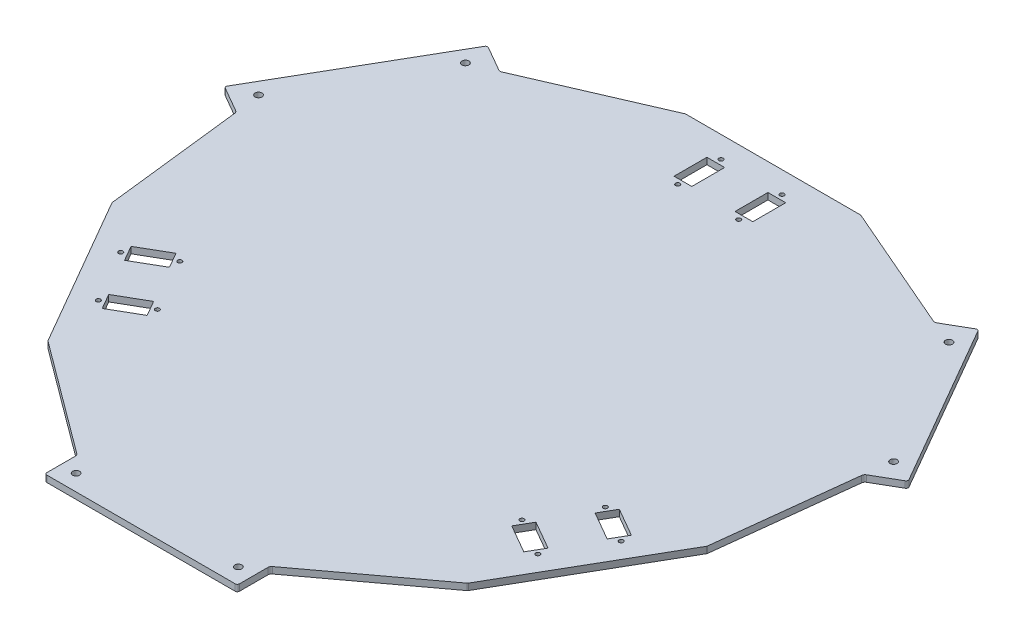
SolidWorks part; units mm, degrees
ref_plane "正面" through (0, 0, 0) normal (0, 0, 1) x (1, 0, 0)
ref_plane "平面" through (0, 0, 0) normal (0, 1, 0) x (1, 0, 0)
ref_plane "右側面" through (0, 0, 0) normal (1, 0, 0) x (0, 0, -1)
sketch "ｽｹｯﾁ1" plane through (0, 0, 0) normal (0, 1, 0) x (1, 0, 0)
  line L4 (82.0098, -128.7548) -> (95.0002, -136.2548)
  line L5 (152.5098, -6.6452) -> (82.0098, -128.7548)
  line L6 (178.6972, -21.2874) -> (185.4854, -9.5298)
  line L7 (185.4854, -7.7798) -> (158.8752, 38.3104)
  line L8 (156.4847, 38.9509) -> (145.7723, 32.7661)
  line L9 (144.9088, 31.4513) -> (137.6417, -31.4843)
  line L10 (138.5051, -33.2006) -> (149.5636, -39.5852)
  line L11 (151.4028, -39.53) -> (178.1458, -21.8728)
  line L12 (178.6972, -21.2874) -> (185.4854, -9.5298)
  line L13 (185.4854, -7.7798) -> (158.8752, 38.3104)
  line L14 (156.4847, 38.9509) -> (145.7723, 32.7661)
  line L15 (144.9088, 31.4513) -> (137.6417, -31.4843)
  line L16 (138.5051, -33.2006) -> (149.5636, -39.5852)
  line L17 (151.4028, -39.53) -> (178.1458, -21.8728)
  line L18 (101.2625, 109.8594) -> (111.9748, 116.0442)
  line L19 (112.6154, 118.4348) -> (86.0052, 164.525)
  line L20 (84.4896, 165.4) -> (70.9131, 165.4)
  line L21 (70.1305, 165.2152) -> (41.4674, 150.8837)
  line L22 (40.5, 149.3184) -> (40.5, 136.5492)
  line L23 (41.5546, 134.9433) -> (99.6921, 109.7691)
  line L24 (101.2625, 109.8594) -> (111.9748, 116.0442)
  line L25 (112.6154, 118.4348) -> (86.0052, 164.525)
  line L26 (84.4896, 165.4) -> (70.9131, 165.4)
  line L27 (70.1305, 165.2152) -> (41.4674, 150.8837)
  line L28 (40.5, 149.3184) -> (40.5, 136.5492)
  line L29 (41.5546, 134.9433) -> (99.6921, 109.7691)
  line L30 (165.5002, -14.1452) -> (152.5098, -6.6452)
  line L31 (95.0002, -136.2548) -> (165.5002, -14.1452)
  line L32 (82.0098, -128.7548) -> (95.0002, -136.2548)
  line L33 (152.5098, -6.6452) -> (82.0098, -128.7548)
  line L34 (165.5002, -14.1452) -> (152.5098, -6.6452)
  line L35 (95.0002, -136.2548) -> (165.5002, -14.1452)
  line L36 (70.5, 135.4) -> (70.5, 150.4)
  line L37 (-70.5, 135.4) -> (70.5, 135.4)
  line L38 (-70.5, 150.4) -> (-70.5, 135.4)
  line L39 (70.5, 150.4) -> (-70.5, 150.4)
  line L40 (70.5, 135.4) -> (70.5, 150.4)
  line L41 (-70.5, 135.4) -> (70.5, 135.4)
  line L42 (-70.5, 150.4) -> (-70.5, 135.4)
  line L43 (70.5, 150.4) -> (-70.5, 150.4)
  line L44 (-74.5098, -141.7452) -> (-74.5098, -156.7452)
  line L45 (74.5102, -141.7452) -> (-74.5098, -141.7452)
  line L46 (-86.0052, 164.525) -> (-112.6154, 118.4348)
  line L47 (-70.9131, 165.4) -> (-84.4896, 165.4)
  line L48 (-41.4674, 150.8837) -> (-70.1305, 165.2152)
  line L49 (-40.5, 136.5492) -> (-40.5, 149.3184)
  line L50 (-99.6921, 109.7691) -> (-41.5546, 134.9433)
  line L51 (-111.9748, 116.0442) -> (-101.2625, 109.8594)
  line L52 (-86.0052, 164.525) -> (-112.6154, 118.4348)
  line L53 (-70.9131, 165.4) -> (-84.4896, 165.4)
  line L54 (-41.4674, 150.8837) -> (-70.1305, 165.2152)
  line L55 (-40.5, 136.5492) -> (-40.5, 149.3184)
  line L56 (-99.6921, 109.7691) -> (-41.5546, 134.9433)
  line L57 (-111.9748, 116.0442) -> (-101.2625, 109.8594)
  line L58 (108.0154, -143.3424) -> (109.9354, -111.3536)
  line L59 (100.9958, -155.8702) -> (107.784, -144.1126)
  line L60 (46.2598, -156.7452) -> (99.4802, -156.7452)
  line L61 (44.5098, -142.6256) -> (44.5098, -154.9952)
  line L62 (96.087, -103.459) -> (45.2168, -141.2204)
  line L63 (109.0636, -109.7332) -> (98.0051, -103.3487)
  line L64 (108.0154, -143.3424) -> (109.9354, -111.3536)
  line L65 (100.9958, -155.8702) -> (107.784, -144.1126)
  line L66 (46.2598, -156.7452) -> (99.4802, -156.7452)
  line L67 (44.5098, -142.6256) -> (44.5098, -154.9952)
  line L68 (96.087, -103.459) -> (45.2168, -141.2204)
  line L69 (109.0636, -109.7332) -> (98.0051, -103.3487)
  line L70 (74.5102, -156.7452) -> (74.5102, -141.7452)
  line L71 (-74.5098, -156.7452) -> (74.5102, -156.7452)
  line L72 (-74.5098, -141.7452) -> (-74.5098, -156.7452)
  line L73 (74.5102, -141.7452) -> (-74.5098, -141.7452)
  line L74 (74.5102, -156.7452) -> (74.5102, -141.7452)
  line L75 (-74.5098, -156.7452) -> (74.5102, -156.7452)
  line L76 (-152.5098, -6.6452) -> (-165.5002, -14.1452)
  line L77 (-82.0098, -128.7548) -> (-152.5098, -6.6452)
  line L78 (-95.0002, -136.2548) -> (-82.0098, -128.7548)
  line L79 (-165.5002, -14.1452) -> (-95.0002, -136.2548)
  line L80 (-152.5098, -6.6452) -> (-165.5002, -14.1452)
  line L81 (-82.0098, -128.7548) -> (-152.5098, -6.6452)
  line L82 (-95.0002, -136.2548) -> (-82.0098, -128.7548)
  line L83 (-165.5002, -14.1452) -> (-95.0002, -136.2548)
  line L84 (173.0004, 13.8449) -> (98.4904, 142.9)
  line L85 (160.01, 6.3449) -> (173.0004, 13.8449)
  line L86 (-99.4802, -156.7452) -> (-46.2598, -156.7452)
  line L87 (-107.784, -144.1126) -> (-100.9958, -155.8702)
  line L88 (-109.9354, -111.3536) -> (-108.0154, -143.3424)
  line L89 (-98.0051, -103.3487) -> (-109.0636, -109.7332)
  line L90 (-45.2168, -141.2204) -> (-96.087, -103.459)
  line L91 (-44.5098, -154.9952) -> (-44.5098, -142.6256)
  line L92 (-99.4802, -156.7452) -> (-46.2598, -156.7452)
  line L93 (-107.784, -144.1126) -> (-100.9958, -155.8702)
  line L94 (-109.9354, -111.3536) -> (-108.0154, -143.3424)
  line L95 (-98.0051, -103.3487) -> (-109.0636, -109.7332)
  line L96 (-45.2168, -141.2204) -> (-96.087, -103.459)
  line L97 (-44.5098, -154.9952) -> (-44.5098, -142.6256)
  line L98 (-185.4854, -9.5298) -> (-178.6972, -21.2874)
  line L99 (-158.8752, 38.3104) -> (-185.4854, -7.7798)
  line L100 (-145.7723, 32.7661) -> (-156.4847, 38.9509)
  line L101 (-137.6417, -31.4843) -> (-144.9088, 31.4513)
  line L102 (-149.5636, -39.5852) -> (-138.5051, -33.2006)
  line L103 (-178.1458, -21.8728) -> (-151.4028, -39.53)
  line L104 (-185.4854, -9.5298) -> (-178.6972, -21.2874)
  line L105 (-158.8752, 38.3104) -> (-185.4854, -7.7798)
  line L106 (-145.7723, 32.7661) -> (-156.4847, 38.9509)
  line L107 (-137.6417, -31.4843) -> (-144.9088, 31.4513)
  line L108 (-149.5636, -39.5852) -> (-138.5051, -33.2006)
  line L109 (-178.1458, -21.8728) -> (-151.4028, -39.53)
  line L110 (85.5, 135.4) -> (160.01, 6.3449)
  line L111 (98.4904, 142.9) -> (85.5, 135.4)
  line L112 (173.0004, 13.8449) -> (98.4904, 142.9)
  line L113 (160.01, 6.3449) -> (173.0004, 13.8449)
  line L114 (85.5, 135.4) -> (160.01, 6.3449)
  line L115 (98.4904, 142.9) -> (85.5, 135.4)
  line L116 (-173.0004, 13.8449) -> (-160.01, 6.3449)
  line L117 (-160.01, 6.3449) -> (-85.5, 135.4)
  line L118 (-85.5, 135.4) -> (-98.4904, 142.9)
  line L119 (-98.4904, 142.9) -> (-173.0004, 13.8449)
  line L120 (-173.0004, 13.8449) -> (-160.01, 6.3449)
  line L121 (-160.01, 6.3449) -> (-85.5, 135.4)
  line L122 (-85.5, 135.4) -> (-98.4904, 142.9)
  line L123 (-98.4904, 142.9) -> (-173.0004, 13.8449)
  line L858 (-40.5, 149.3184) -> (-40.5, 150.4)
  line L859 (40.5, 149.3184) -> (40.5, 150.4)
  line L860 (111.9748, 116.0442) -> (113.4904, 116.9192)
  line L861 (156.4847, 38.9509) -> (158.0002, 39.8259)
  line L862 (149.5636, -39.5852) -> (150.5002, -40.126)
  line L863 (109.0636, -109.7332) -> (110.0002, -110.274)
  line L864 (-109.0636, -109.7332) -> (-110.0002, -110.274)
  line L865 (-149.5636, -39.5852) -> (-150.5002, -40.126)
  line L866 (-156.4847, 38.9509) -> (-158.0002, 39.8259)
  line L867 (-111.9748, 116.0442) -> (-113.4904, 116.9192)
  line L868 (96.087, -103.459) -> (97.0098, -102.774)
  line L869 (-44.5098, -154.9952) -> (-44.5098, -156.7452)
  line L3810 (-41.5546, 134.9433) -> (-40.5, 135.4)
  line L3811 (41.5546, 134.9433) -> (40.5, 135.4)
  line L3812 (44.5098, -154.9952) -> (44.5098, -156.7452)
  line L3813 (-137.6417, -31.4843) -> (-137.5098, -32.626)
  line L3814 (-96.087, -103.459) -> (-97.0098, -102.774)
  line L3815 (137.6417, -31.4843) -> (137.5098, -32.626)
  arc A6 (185.4854, -9.5298) -> (185.4854, -7.7798) centre (183.9699, -8.6548) ccw
  arc A7 (158.8752, 38.3104) -> (156.4847, 38.9509) centre (157.3597, 37.4354) ccw
  arc A8 (145.7723, 32.7661) -> (144.9088, 31.4513) centre (146.6473, 31.2506) ccw
  arc A9 (137.6417, -31.4843) -> (138.5051, -33.2006) centre (139.3801, -31.685) ccw
  arc A10 (149.5636, -39.5852) -> (151.4028, -39.53) centre (150.4386, -38.0696) ccw
  arc A11 (178.1458, -21.8728) -> (178.6972, -21.2874) centre (177.1816, -20.4124) ccw
  arc A12 (185.4854, -9.5298) -> (185.4854, -7.7798) centre (183.9699, -8.6548) ccw
  arc A13 (158.8752, 38.3104) -> (156.4847, 38.9509) centre (157.3597, 37.4354) ccw
  arc A14 (145.7723, 32.7661) -> (144.9088, 31.4513) centre (146.6473, 31.2506) ccw
  arc A15 (137.6417, -31.4843) -> (138.5051, -33.2006) centre (139.3801, -31.685) ccw
  arc A16 (149.5636, -39.5852) -> (151.4028, -39.53) centre (150.4386, -38.0696) ccw
  arc A17 (178.1458, -21.8728) -> (178.6972, -21.2874) centre (177.1816, -20.4124) ccw
  arc A18 (111.9748, 116.0442) -> (112.6154, 118.4348) centre (111.0998, 117.5598) ccw
  arc A19 (86.0052, 164.525) -> (84.4896, 165.4) centre (84.4896, 163.65) ccw
  arc A20 (70.9131, 165.4) -> (70.1305, 165.2152) centre (70.9131, 163.65) ccw
  arc A21 (41.4674, 150.8837) -> (40.5, 149.3184) centre (42.25, 149.3184) ccw
  arc A22 (40.5, 136.5492) -> (41.5546, 134.9433) centre (42.25, 136.5492) ccw
  arc A23 (99.6921, 109.7691) -> (101.2625, 109.8594) centre (100.3875, 111.375) ccw
  arc A24 (111.9748, 116.0442) -> (112.6154, 118.4348) centre (111.0998, 117.5598) ccw
  arc A25 (86.0052, 164.525) -> (84.4896, 165.4) centre (84.4896, 163.65) ccw
  arc A26 (70.9131, 165.4) -> (70.1305, 165.2152) centre (70.9131, 163.65) ccw
  arc A27 (41.4674, 150.8837) -> (40.5, 149.3184) centre (42.25, 149.3184) ccw
  arc A28 (40.5, 136.5492) -> (41.5546, 134.9433) centre (42.25, 136.5492) ccw
  arc A29 (99.6921, 109.7691) -> (101.2625, 109.8594) centre (100.3875, 111.375) ccw
  arc A30 (-84.4896, 165.4) -> (-86.0052, 164.525) centre (-84.4896, 163.65) ccw
  arc A31 (-70.1305, 165.2152) -> (-70.9131, 165.4) centre (-70.9131, 163.65) ccw
  arc A32 (-40.5, 149.3184) -> (-41.4674, 150.8837) centre (-42.25, 149.3184) ccw
  arc A33 (-41.5546, 134.9433) -> (-40.5, 136.5492) centre (-42.25, 136.5492) ccw
  arc A34 (-101.2625, 109.8594) -> (-99.6921, 109.7691) centre (-100.3875, 111.375) ccw
  arc A35 (-112.6154, 118.4348) -> (-111.9748, 116.0442) centre (-111.0998, 117.5598) ccw
  arc A36 (-84.4896, 165.4) -> (-86.0052, 164.525) centre (-84.4896, 163.65) ccw
  arc A37 (-70.1305, 165.2152) -> (-70.9131, 165.4) centre (-70.9131, 163.65) ccw
  arc A38 (-40.5, 149.3184) -> (-41.4674, 150.8837) centre (-42.25, 149.3184) ccw
  arc A39 (-41.5546, 134.9433) -> (-40.5, 136.5492) centre (-42.25, 136.5492) ccw
  arc A40 (-101.2625, 109.8594) -> (-99.6921, 109.7691) centre (-100.3875, 111.375) ccw
  arc A41 (-112.6154, 118.4348) -> (-111.9748, 116.0442) centre (-111.0998, 117.5598) ccw
  arc A42 (107.784, -144.1126) -> (108.0154, -143.3424) centre (106.2685, -143.2376) ccw
  arc A43 (99.4802, -156.7452) -> (100.9958, -155.8702) centre (99.4802, -154.9952) ccw
  arc A44 (44.5098, -154.9952) -> (46.2598, -156.7452) centre (46.2598, -154.9952) ccw
  arc A45 (45.2168, -141.2204) -> (44.5098, -142.6256) centre (46.2598, -142.6256) ccw
  arc A46 (98.0051, -103.3487) -> (96.087, -103.459) centre (97.1301, -104.8642) ccw
  arc A47 (109.9354, -111.3536) -> (109.0636, -109.7332) centre (108.1886, -111.2488) ccw
  arc A48 (107.784, -144.1126) -> (108.0154, -143.3424) centre (106.2685, -143.2376) ccw
  arc A49 (99.4802, -156.7452) -> (100.9958, -155.8702) centre (99.4802, -154.9952) ccw
  arc A50 (44.5098, -154.9952) -> (46.2598, -156.7452) centre (46.2598, -154.9952) ccw
  arc A51 (45.2168, -141.2204) -> (44.5098, -142.6256) centre (46.2598, -142.6256) ccw
  arc A52 (98.0051, -103.3487) -> (96.087, -103.459) centre (97.1301, -104.8642) ccw
  arc A53 (109.9354, -111.3536) -> (109.0636, -109.7332) centre (108.1886, -111.2488) ccw
  arc A54 (-100.9958, -155.8702) -> (-99.4802, -156.7452) centre (-99.4802, -154.9952) ccw
  arc A55 (-108.0154, -143.3424) -> (-107.784, -144.1126) centre (-106.2685, -143.2376) ccw
  arc A56 (-109.0636, -109.7332) -> (-109.9354, -111.3536) centre (-108.1886, -111.2488) ccw
  arc A57 (-96.087, -103.459) -> (-98.0051, -103.3487) centre (-97.1301, -104.8642) ccw
  arc A58 (-44.5098, -142.6256) -> (-45.2168, -141.2204) centre (-46.2598, -142.6256) ccw
  arc A59 (-46.2598, -156.7452) -> (-44.5098, -154.9952) centre (-46.2598, -154.9952) ccw
  arc A60 (-100.9958, -155.8702) -> (-99.4802, -156.7452) centre (-99.4802, -154.9952) ccw
  arc A61 (-108.0154, -143.3424) -> (-107.784, -144.1126) centre (-106.2685, -143.2376) ccw
  arc A62 (-109.0636, -109.7332) -> (-109.9354, -111.3536) centre (-108.1886, -111.2488) ccw
  arc A63 (-96.087, -103.459) -> (-98.0051, -103.3487) centre (-97.1301, -104.8642) ccw
  arc A64 (-44.5098, -142.6256) -> (-45.2168, -141.2204) centre (-46.2598, -142.6256) ccw
  arc A65 (-46.2598, -156.7452) -> (-44.5098, -154.9952) centre (-46.2598, -154.9952) ccw
  arc A66 (-185.4854, -7.7798) -> (-185.4854, -9.5298) centre (-183.9699, -8.6548) ccw
  arc A67 (-156.4847, 38.9509) -> (-158.8752, 38.3104) centre (-157.3597, 37.4354) ccw
  arc A68 (-144.9088, 31.4513) -> (-145.7723, 32.7661) centre (-146.6473, 31.2506) ccw
  arc A69 (-138.5051, -33.2006) -> (-137.6417, -31.4843) centre (-139.3801, -31.685) ccw
  arc A70 (-151.4028, -39.53) -> (-149.5636, -39.5852) centre (-150.4386, -38.0696) ccw
  arc A71 (-178.6972, -21.2874) -> (-178.1458, -21.8728) centre (-177.1816, -20.4124) ccw
  arc A72 (-185.4854, -7.7798) -> (-185.4854, -9.5298) centre (-183.9699, -8.6548) ccw
  arc A73 (-156.4847, 38.9509) -> (-158.8752, 38.3104) centre (-157.3597, 37.4354) ccw
  arc A74 (-144.9088, 31.4513) -> (-145.7723, 32.7661) centre (-146.6473, 31.2506) ccw
  arc A75 (-138.5051, -33.2006) -> (-137.6417, -31.4843) centre (-139.3801, -31.685) ccw
  arc A76 (-151.4028, -39.53) -> (-149.5636, -39.5852) centre (-150.4386, -38.0696) ccw
  arc A77 (-178.6972, -21.2874) -> (-178.1458, -21.8728) centre (-177.1816, -20.4124) ccw
  dimension "D1" = 0
  dimension "D2" = 0
  dimension "D3" = 0
  dimension "D4" = 0
  dimension "D5" = 0
  dimension "D6" = 0
  dimension "D7" = 0
  dimension "D8" = 0
  dimension "D9" = 0
  dimension "D10" = 0
  dimension "D11" = 0
  dimension "D12" = 0
extrude "ﾎﾞｽ - 押し出し2" add sketch "ｽｹｯﾁ1" along normal mid plane 3 contours A75 L81 A63 L96 L73 A51 L68 A52 L33 A15 L15 A14 L114 A29 L29 L3811 L41 L3810 L56 A40 L121 A74 L107 | A64 L97 L869 L75 L3812 L67 A51 L73 | A74 L121 A40 L57 L867 L123 L866 L106 | A29 L114 A14 L14 L861 L112 L860 L24 region at (0, 0, 0) region at (0, 0, 149.2444) region at (129.2495, 0, -74.6222) region at (-129.2495, 0, -74.6222)
fillet "ﾌｨﾚｯﾄ1" radius 1 12 edges at (-158.0002, 0, -39.8259) (-113.4904, 0, -116.9192) (113.4904, 0, -116.9192) (158.0002, 0, -39.8259) (-40.5, 0, -135.4) (40.5, 0, -135.4) (137.5098, 0, 32.626) (97.0098, 0, 102.774) (44.5098, 0, 156.7452) (-44.5098, 0, 156.7452) (-97.0098, 0, 102.774) (-137.5098, 0, 32.626)
sketch "ｽｹｯﾁ3" plane through (0, -1.5, 0) normal (0, -1, 0) x (1, 0, 0)
  line L0 (135.7453, -78.3726) -> (129.2501, -74.6226) construction
  line L1 (157.5002, -40.692) -> (113.9904, -116.0532) construction
  line L2 (129.2501, -74.6226) -> (111.7501, -104.9335) construction
  circle A0 centre (111.7501, -104.9335) radius 1.6
  circle A1 centre (146.7501, -44.3117) radius 1.6
  dimension "D3" = 3.2
  dimension "D1" = 7.5
  dimension "D2" = 35
extrude "ｶｯﾄ - 押し出し1" cut sketch "ｽｹｯﾁ3" against normal through all both and the other way through all
mirror "ﾐﾗｰ1" about plane through (0, 0, 0) normal (1, 0, 0) of "ｶｯﾄ - 押し出し1"
sketch "ｽｹｯﾁ4" plane through (0, -1.5, 0) normal (0, -1, 0) x (1, 0, 0)
  circle A0 centre (37.5002, 149.2452) radius 1.6 construction
  circle A1 centre (-37.4998, 149.2502) radius 1.6 construction
  circle A2 centre (37.5002, 149.2452) radius 1.6
  circle A3 centre (-37.4998, 149.2502) radius 1.6
extrude "ｶｯﾄ - 押し出し2" cut sketch "ｽｹｯﾁ4" against normal through all both and the other way through all
sketch "ｽｹｯﾁ5" plane through (0, 1.5, 0) normal (0, 1, 0) x (1, 0, 0)
  line L0 (-117.2598, -67.7) -> (-99.9393, -57.7) construction
  line L1 (-97.1134, -102.5946) -> (-137.4062, -32.8054) construction
  line L2 (-99.9393, -57.7) -> (-104.9393, -49.0397) construction
  line L3 (-115.6211, -45.7383) -> (-102.4575, -38.1383)
  line L4 (-102.4575, -38.1383) -> (-98.3575, -45.2397)
  line L5 (-98.3575, -45.2397) -> (-111.5211, -52.8397)
  line L6 (-111.5211, -52.8397) -> (-115.6211, -45.7383)
  line L7 (-101.5211, -70.1603) -> (-97.4211, -77.2617)
  line L8 (-88.3575, -62.5603) -> (-101.5211, -70.1603)
  line L9 (-84.2575, -69.6617) -> (-88.3575, -62.5603)
  line L10 (-97.4211, -77.2617) -> (-84.2575, -69.6617)
  circle A0 centre (-98.3291, -40.489) radius 1 construction
  circle A1 centre (-98.3291, -40.489) radius 1
  circle A2 centre (-115.6496, -50.489) radius 1 construction
  circle A3 centre (-115.6496, -50.489) radius 1
  circle A4 centre (-101.5496, -74.911) radius 1
  circle A5 centre (-84.2291, -64.911) radius 1
  point P7 (-104.9393, -49.0397)
  point P20 (0, 0)
  dimension "D1" = 20
  dimension "D2" = 10
  dimension "D3" = 15.2
  dimension "D4" = 8.2
extrude "ｶｯﾄ - 押し出し3" cut sketch "ｽｹｯﾁ5" against normal through all both and the other way through all
ref_axis "軸1" through (0, 1.65, 0) along (0, -1, 0)
pattern_circular "円形ﾊﾟﾀｰﾝ1" count 3 over 360 about axis through (0, 1.65, 0) along (0, -1, 0) of "ｶｯﾄ - 押し出し3"
